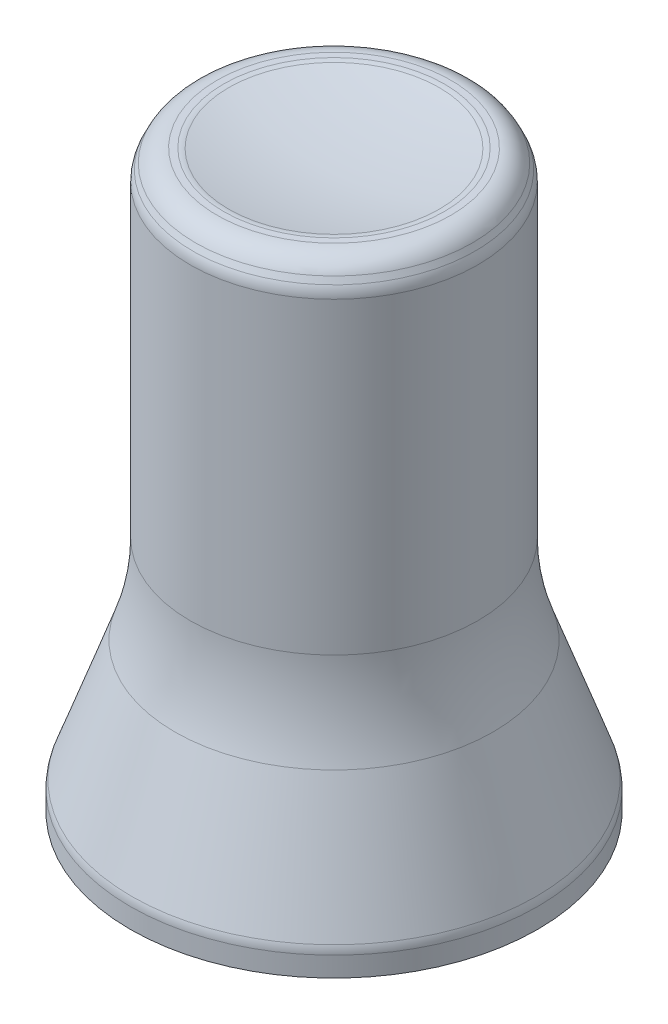
SolidWorks part; units mm, degrees
ref_plane "Front Plane" through (0, 0, 0) normal (0, 0, 1) x (1, 0, 0)
ref_plane "Top Plane" through (0, 0, 0) normal (0, 1, 0) x (1, 0, 0)
ref_plane "Right Plane" through (0, 0, 0) normal (1, 0, 0) x (0, 0, -1)
sketch "Sketch1" plane through (0, 0, 0) normal (0, 0, 1) x (1, 0, 0)
  line L0 (0, 0) -> (8.5, 0)
  line L1 (8.5, 0) -> (8.5, 1)
  line L2 (8.5, 1) -> (6, 8)
  line L3 (6, 8) -> (6, 23)
  line L4 (6, 23) -> (5.5, 24)
  line L5 (5.5, 24) -> (4.5, 24)
  line L6 (4.5, 24) -> (2.2778, 23.5) construction
  line L7 (0, 23.5) -> (0, 0) construction
  line L8 (0, 0) -> (0, 23.5)
  line L9 (2.2778, 23.5) -> (0, 23.5) construction
  spline S0 degree 2 poles (4.5, 24) (2.2778, 23.5) (0, 23.5) knots 0 0 0 1 1 1
  dimension "D1" = 24
  dimension "D2" = 6
  dimension "D3" = 1
  dimension "D4" = 8
  dimension "D5" = 1
  dimension "D6" = 0.5
  dimension "D7" = 0.5
  dimension "D8" = 1
  dimension "D9" = 8.5
revolve "Revolve1" add sketch "Sketch1" angle 360 about L7
fillet "Fillet1" radius 11 1 edges at (-6, 8, 0)
fillet "Fillet2" radius 1 4 edges at (-4.5, 24, 0) (-5.5, 24, 0) (-6, 23, 0) (-8.5, 1, 0)
sketch "Sketch3" plane through (0, 0, 0) normal (0, 0, 1) x (1, 0, 0)
  line L0 (0, 0) -> (3.875, 0)
  line L1 (-8.5, 0) -> (8.5, 0) construction
  line L2 (3.875, 0) -> (3.875, 6.5)
  line L3 (3.875, 6.5) -> (3.05, 7.325)
  line L4 (3.05, 7.325) -> (3.05, 17.75)
  line L5 (3.05, 17.75) -> (0, 17.75)
  line L6 (0, 17.75) -> (0, 0)
  dimension "D1" = 17.75
  dimension "D2" = 3.875
  dimension "D3" = 45
  dimension "D4" = 3.05
  dimension "D5" = 6.5
revolve "Cut-Revolve1" cut sketch "Sketch3" angle 360 about L6
ref_plane "Plane1" through (0, 7.325, 0) normal (0, 1, 0) x (1, 0, 0)
sketch "Sketch4" plane through (0, 17.75, 0) normal (0, -1, 0) x (1, 0, 0)
  line L0 (-999.9068, -3) -> (49000.0932, -3) construction
  line L1 (-2.6557, 4.6) -> (2.6557, 4.6)
  line L2 (-2.6557, 4.6) -> (-2.6557, 1.5)
  line L3 (-2.6557, 1.5) -> (2.6557, 1.5)
  line L4 (2.6557, 4.6) -> (2.6557, 1.5)
  line L5 (-2.6557, 4.6) -> (2.6557, 1.5) construction
  line L6 (-2.6557, 1.5) -> (2.6557, 4.6) construction
  line L7 (9.35, 0) -> (-9.35, 0) construction
  circle A0 centre (0, 0) radius 3.05 construction
  circle A1 centre (0, 0) radius 3.05 construction
  circle A2 centre (0, -3.05) radius 0.1
  point P0 (0, 3.05)
  dimension "D1" = 3
  dimension "D3" = 0.2
  dimension "D2" = 4.5
extrude "Boss-Extrude1" add sketch "Sketch4" along normal up to surface (10.425 mm away) up to plane "Plane1"
chamfer "Chamfer1" distance 0.35 angle 45 1 edges at (0, 7.325, 1.5)
